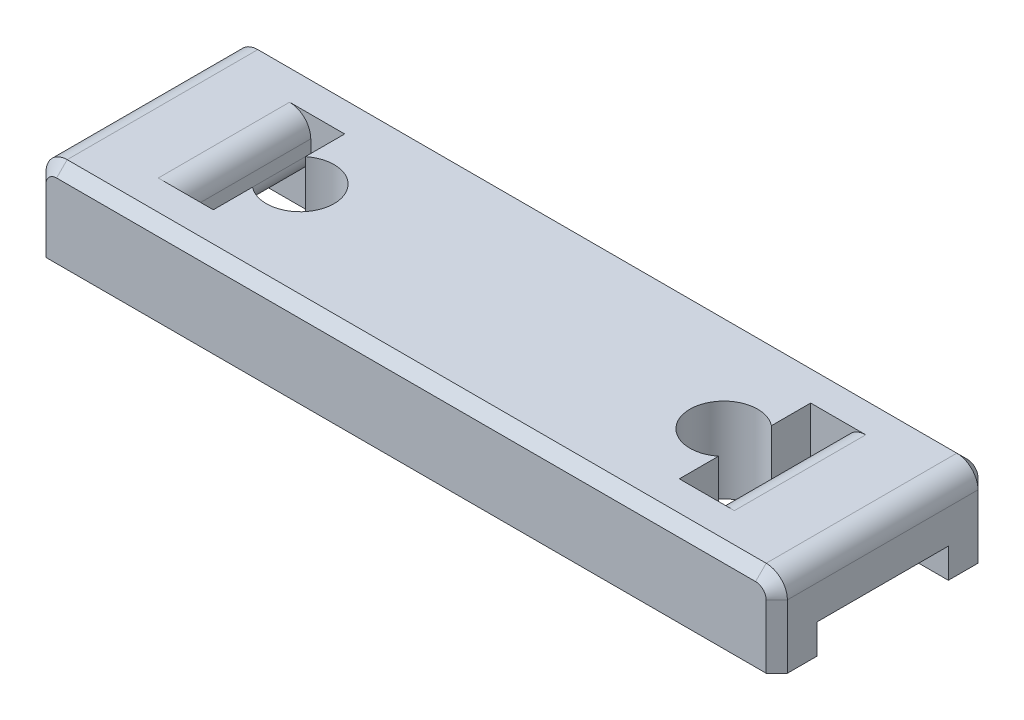
SolidWorks part; units mm, degrees
ref_plane "Front Plane" through (0, 0, 0) normal (0, 0, 1) x (1, 0, 0)
ref_plane "Top Plane" through (0, 0, 0) normal (0, 1, 0) x (1, 0, 0)
ref_plane "Right Plane" through (0, 0, 0) normal (1, 0, 0) x (0, 0, -1)
sketch "Sketch2" plane through (0, 0, 0) normal (0, 1, 0) x (1, 0, 0)
  line L1 (-17.5, -5) -> (17.5, -5)
  line L2 (-17.5, -5) -> (-17.5, 5)
  line L3 (-17.5, 5) -> (17.5, 5)
  line L4 (17.5, -5) -> (17.5, 5)
  line L5 (-17.5, -5) -> (17.5, 5) construction
  line L6 (-17.5, 5) -> (17.5, -5) construction
  point P0 (0, 0)
  dimension "D1" = 35
  dimension "D2" = 10
extrude "Boss-Extrude1" add sketch "Sketch2" along normal blind 4
sketch "Sketch3" plane through (0, 4, 0) normal (0, 1, 0) x (1, 0, 0)
  line L0 (0, 5) -> (0, -5) construction
  line L1 (17.5, 5) -> (-17.5, 5) construction
  line L2 (-17.5, -5) -> (17.5, -5) construction
  line L3 (-17.5, 0) -> (17.5, 0) construction
  line L4 (-17.5, 5) -> (-17.5, -5) construction
  line L5 (17.5, -5) -> (17.5, 5) construction
  line L6 (-11, 1.249) -> (-11, 3.1)
  line L7 (-12.6, -3.1) -> (-11, -3.1)
  line L8 (-12.6, -3.1) -> (-12.6, 3.1)
  line L9 (-12.6, 3.1) -> (-11, 3.1)
  line L10 (-11, -3.1) -> (-11, -1.249)
  line L11 (-12.6, -3.1) -> (-11, 3.1) construction
  line L12 (-12.6, 3.1) -> (-11, -3.1) construction
  line L13 (11, -3.1) -> (11, -1.249)
  line L14 (12.6, -3.1) -> (11, -3.1)
  line L15 (12.6, -3.1) -> (12.6, 3.1)
  line L16 (12.6, 3.1) -> (11, 3.1)
  line L17 (11, 1.249) -> (11, 3.1)
  arc A0 (-11, -1.249) -> (-11, 1.249) centre (-10, 0) ccw
  arc A1 (11, -1.249) -> (11, 1.249) centre (10, 0) cw
  point P14 (-11.8, 0)
  point P19 (-11.6, 0)
  dimension "D1" = 3.2
  dimension "D2" = 20
  dimension "D3" = 1.8
  dimension "D4" = 6.2
  dimension "D5" = 1.6
extrude "Cut-Extrude1" cut sketch "Sketch3" against normal up to surface (4 mm away) up to face at (0, 0, 0)
sketch "Sketch4" plane through (-17.5, 0, 0) normal (-1, 0, 0) x (0, 0, 1)
  line L0 (0, 4) -> (0, 0) construction
  line L1 (-5, 4) -> (5, 4) construction
  line L2 (-3.1, 0) -> (-3.1, 1.4)
  line L3 (-5, 0) -> (5, 0) construction
  line L4 (-3.1, 1.4) -> (3.1, 1.4)
  line L5 (-3.1, 0) -> (3.1, 0)
  line L6 (3.1, 0) -> (3.1, 1.4)
  point P11 (0, 1.4)
  dimension "D1" = 1.4
  dimension "D2" = 6.2
extrude "Cut-Extrude2" cut sketch "Sketch4" against normal up to surface (4.9 mm away) up to face at (-12.6, 2, 0)
sketch "Sketch5" plane through (17.5, 0, 0) normal (1, 0, 0) x (0, 0, -1)
  line L0 (0, 4) -> (0, 0) construction
  line L1 (-5, 4) -> (5, 4) construction
  line L2 (-5, 0) -> (5, 0) construction
  line L3 (3.1, 0) -> (-3.1, 0)
  line L4 (-3.1, 0) -> (-3.1, 1.4)
  line L5 (-3.1, 1.4) -> (3.1, 1.4)
  line L6 (3.1, 0) -> (3.1, 1.4)
  point P10 (0, 1.4)
  dimension "D1" = 1.4
  dimension "D2" = 6.2
extrude "Cut-Extrude3" cut sketch "Sketch5" against normal up to surface (4.9 mm away) up to face at (12.6, 2, 0)
fillet "Fillet1" radius 1 4 edges at (-12.6, 1.4, 0) (12.6, 4, 0) (-12.6, 4, 0) (12.6, 1.4, 0)
fillet "Fillet2" radius 1 2 edges at (-17.5, 4, 0) (17.5, 4, 0)
chamfer "Chamfer1" distance 0.5 angle 45 10 edges at (17.5, 1.5, -5) (-17.5, 1.5, -5) (17.2071, 3.7071, -5) (-17.2071, 3.7071, -5) (0, 4, -5) (17.5, 1.5, 5) (17.2071, 3.7071, 5) (0, 4, 5) (-17.2071, 3.7071, 5) (-17.5, 1.5, 5)
